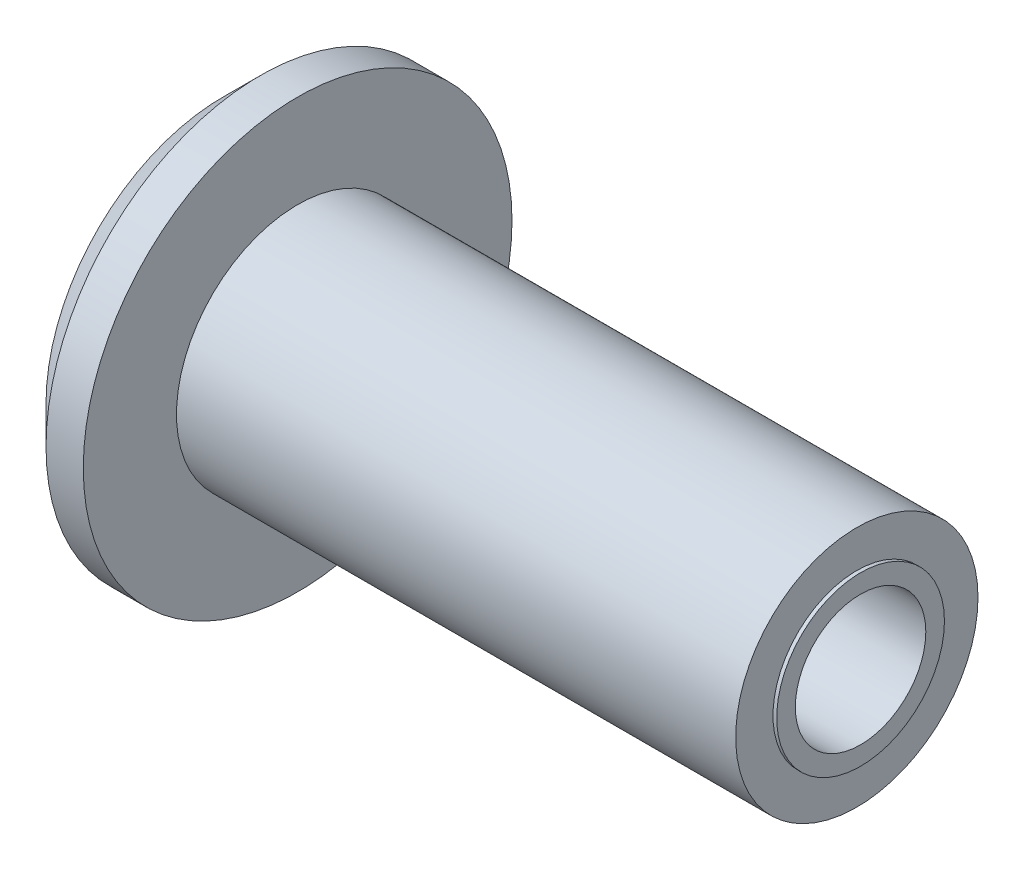
SolidWorks part; units mm, degrees
ref_plane "Front Plane" through (0, 0, 0) normal (0, 0, 1) x (1, 0, 0)
ref_plane "Top Plane" through (0, 0, 0) normal (0, 1, 0) x (1, 0, 0)
ref_plane "Right Plane" through (0, 0, 0) normal (1, 0, 0) x (0, 0, -1)
sketch "Sketch1" plane through (0, 0, 0) normal (1, 0, 0) x (0, 0, -1)
  circle A0 centre (0, 0) radius 3.5
  circle A1 centre (0, 0) radius 6.5
  circle A2 centre (0, 0) radius 0.5
  dimension "D1" = 7
  dimension "D2" = 3
  dimension "D3" = 3
extrude "Boss-Extrude1" add sketch "Sketch1" along normal blind 30 contours A1 A0 region at (0, 0, 6.3162)
sketch "Sketch2" plane through (0, 0, 0) normal (-1, 0, 0) x (0, 0, 1)
  circle A1 centre (0, 0) radius 6.5
  circle A2 centre (0, 0) radius 6.5 construction
  circle A4 centre (0, 0) radius 11.5
  circle A5 centre (0, 0) radius 11.5
  circle A6 centre (0, 0) radius 3.5
  circle A7 centre (0, 0) radius 3.5
  dimension "D1" = 0
  dimension "D2" = 5
  dimension "D3" = 3
extrude "Boss-Extrude2" add sketch "Sketch2" along normal blind 4
sketch "Sketch3" plane through (-4, 0, 0) normal (-1, 0, 0) x (0, 0, 1)
  circle A0 centre (0, 0) radius 6.75
  dimension "D1" = 13.5
extrude "Cut-Extrude1" cut sketch "Sketch3" against normal blind 2
chamfer "Chamfer1" distance 2 angle 45 1 edges at (-4, 0, 11.5)
sketch "Sketch5" plane through (30, 0, 0) normal (1, 0, 0) x (0, 0, -1)
  circle A0 centre (0, 0) radius 3.5 construction
  circle A1 centre (0, 0) radius 3.5
  circle A2 centre (0, 0) radius 4.5
  dimension "D1" = 1
extrude "Boss-Extrude3" add sketch "Sketch5" along normal blind 0.2
